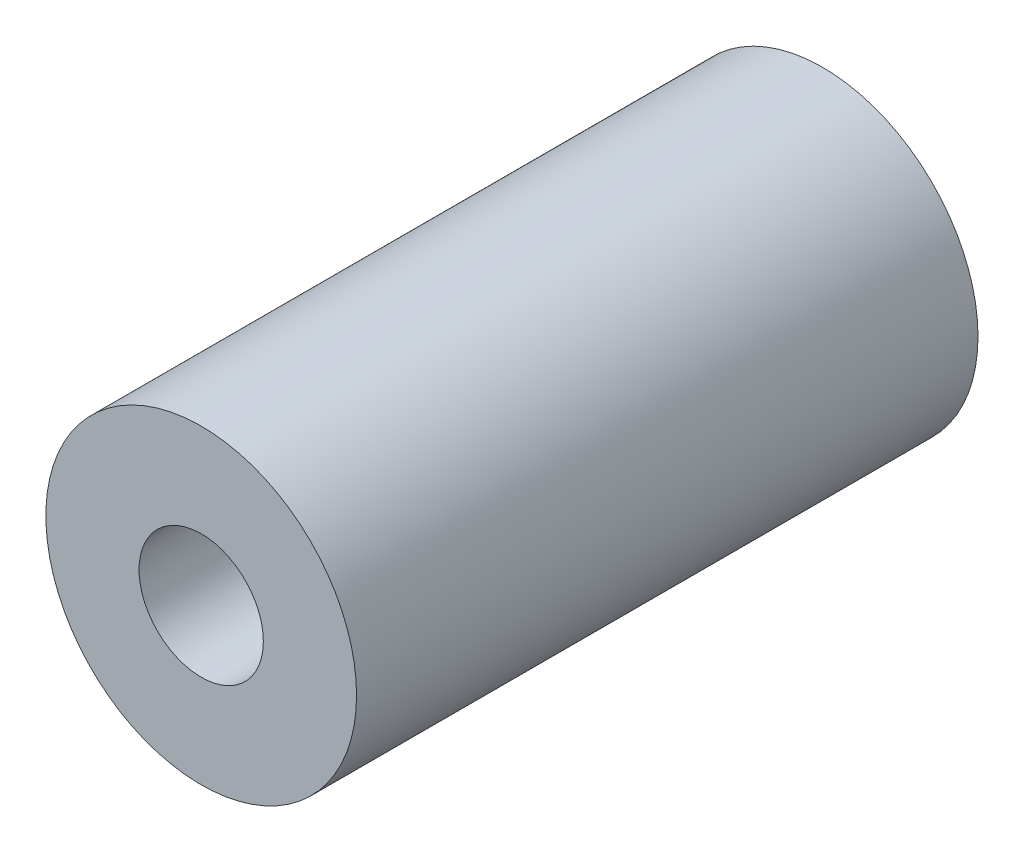
SolidWorks part; units mm, degrees
ref_plane "Front Plane" through (0, 0, 0) normal (0, 0, 1) x (1, 0, 0)
ref_plane "Top Plane" through (0, 0, 0) normal (0, 1, 0) x (1, 0, 0)
ref_plane "Right Plane" through (0, 0, 0) normal (1, 0, 0) x (0, 0, -1)
sketch "Sketch1" plane through (0, 0, 0) normal (0, 0, 1) x (1, 0, 0)
  circle A0 centre (0, 0) radius 9.525
  circle A1 centre (0, 0) radius 3.81
  dimension "D1" = 19.05
  dimension "D2" = 7.62
extrude "Boss-Extrude1" add sketch "Sketch1" along normal blind 19.05 and the other way blind 19.05
